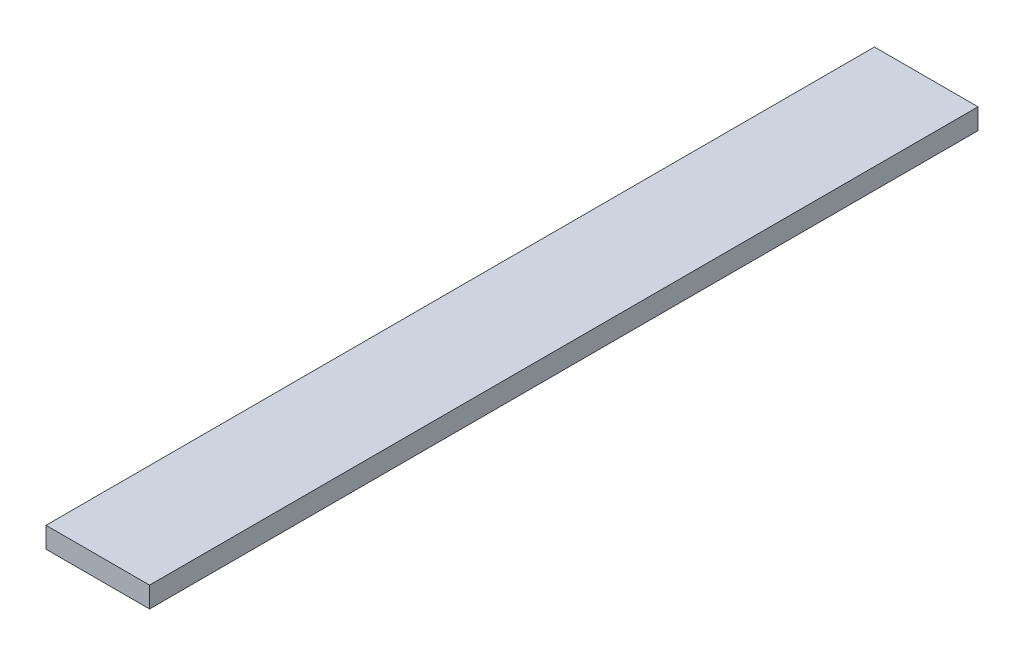
SolidWorks part; units mm, degrees
ref_plane "Front Plane" through (0, 0, 0) normal (0, 0, 1) x (1, 0, 0)
ref_plane "Top Plane" through (0, 0, 0) normal (0, 1, 0) x (1, 0, 0)
ref_plane "Right Plane" through (0, 0, 0) normal (1, 0, 0) x (0, 0, -1)
sketch "Sketch1" plane through (0, 0, 0) normal (0, 1, 0) x (1, 0, 0)
  line L1 (-7.5, 60) -> (7.5, 60)
  line L2 (-7.5, 60) -> (-7.5, -60)
  line L3 (-7.5, -60) -> (7.5, -60)
  line L4 (7.5, 60) -> (7.5, -60)
  line L5 (-7.5, 60) -> (7.5, -60) construction
  line L6 (-7.5, -60) -> (7.5, 60) construction
  point P0 (0, 0)
extrude "Boss-Extrude1" add sketch "Sketch1" along normal blind 3 contours L4 L1 L2 L3 region at (0, 0, 0)
